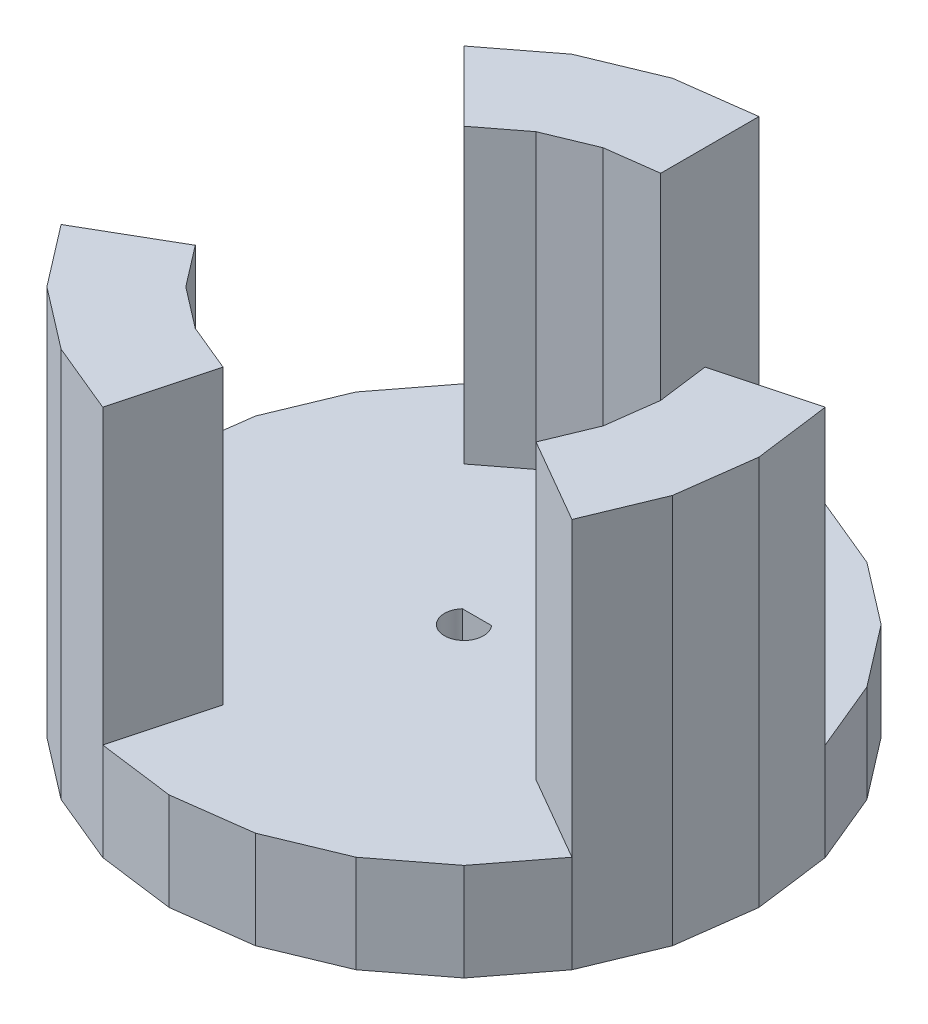
SolidWorks part; units mm, degrees
ref_plane "Front Plane" through (0, 0, 0) normal (0, 0, 1) x (1, 0, 0)
ref_plane "Top Plane" through (0, 0, 0) normal (0, 1, 0) x (1, 0, 0)
ref_plane "Right Plane" through (0, 0, 0) normal (1, 0, 0) x (0, 0, -1)
sketch "Sketch1" plane through (0, 0, 0) normal (0, 1, 0) x (1, 0, 0)
  line L0 (-14.2664, 14.2664) -> (-21.3898, 21.3898)
  line L1 (30.2497, 0) -> (29.219, 7.8292)
  line L2 (29.219, 7.8292) -> (26.197, 15.1248)
  line L3 (26.197, 15.1248) -> (21.3898, 21.3898)
  line L4 (21.3898, 21.3898) -> (15.1248, 26.197)
  line L5 (15.1248, 26.197) -> (7.8292, 29.219)
  line L6 (7.8292, 29.219) -> (0, 30.2497)
  line L7 (0, 30.2497) -> (-7.8292, 29.219)
  line L8 (-7.8292, 29.219) -> (-15.1248, 26.197)
  line L9 (-15.1248, 26.197) -> (-21.3898, 21.3898)
  line L10 (-21.3898, 21.3898) -> (-26.197, 15.1248)
  line L11 (-26.197, 15.1248) -> (-29.219, 7.8292)
  line L12 (-29.219, 7.8292) -> (-30.2497, 0)
  line L13 (-30.2497, 0) -> (-29.219, -7.8292)
  line L14 (-29.219, -7.8292) -> (-26.197, -15.1248)
  line L15 (-26.197, -15.1248) -> (-21.3898, -21.3898)
  line L16 (-21.3898, -21.3898) -> (-15.1248, -26.197)
  line L17 (-15.1248, -26.197) -> (-7.8292, -29.219)
  line L18 (-7.8292, -29.219) -> (0, -30.2497)
  line L19 (0, -30.2497) -> (7.8292, -29.219)
  line L20 (7.8292, -29.219) -> (15.1248, -26.197)
  line L21 (15.1248, -26.197) -> (21.3898, -21.3898)
  line L22 (21.3898, -21.3898) -> (26.197, -15.1248)
  line L23 (26.197, -15.1248) -> (29.219, -7.8292)
  line L24 (29.219, -7.8292) -> (30.2497, 0)
  line L25 (20.1758, 0) -> (19.4883, 5.2219)
  line L26 (19.4883, 5.2219) -> (17.4727, 10.0879)
  line L27 (17.4727, 10.0879) -> (14.2664, 14.2664)
  line L28 (14.2664, 14.2664) -> (10.0879, 17.4727)
  line L29 (10.0879, 17.4727) -> (5.2219, 19.4883)
  line L30 (5.2219, 19.4883) -> (0, 20.1758)
  line L31 (0, 20.1758) -> (-5.2219, 19.4883)
  line L32 (-5.2219, 19.4883) -> (-10.0879, 17.4727)
  line L33 (-10.0879, 17.4727) -> (-14.2664, 14.2664)
  line L34 (-14.2664, 14.2664) -> (-17.4727, 10.0879)
  line L35 (-17.4727, 10.0879) -> (-19.4883, 5.2219)
  line L36 (-19.4883, 5.2219) -> (-20.1758, 0)
  line L37 (-20.1758, 0) -> (-19.4883, -5.2219)
  line L38 (-19.4883, -5.2219) -> (-17.4727, -10.0879)
  line L39 (-17.4727, -10.0879) -> (-14.2664, -14.2664)
  line L40 (-14.2664, -14.2664) -> (-10.0879, -17.4727)
  line L41 (-10.0879, -17.4727) -> (-5.2219, -19.4883)
  line L42 (-5.2219, -19.4883) -> (0, -20.1758)
  line L43 (0, -20.1758) -> (5.2219, -19.4883)
  line L44 (5.2219, -19.4883) -> (10.0879, -17.4727)
  line L45 (10.0879, -17.4727) -> (14.2664, -14.2664)
  line L46 (14.2664, -14.2664) -> (17.4727, -10.0879)
  line L47 (17.4727, -10.0879) -> (19.4883, -5.2219)
  line L48 (19.4883, -5.2219) -> (20.1758, 0)
  line L49 (0, 20.1758) -> (0, 30.2497)
  line L50 (19.4883, 5.2219) -> (29.219, 7.8292)
  line L51 (17.4727, -10.0879) -> (26.197, -15.1248)
  line L52 (-5.2219, -19.4883) -> (-7.8292, -29.219)
  line L53 (-17.4727, -10.0879) -> (-26.197, -15.1248)
  line L54 (-1.4978, 1.3253) -> (1.4978, 1.3253)
  circle A0 centre (0, 0) radius 29.9909 construction
  circle A1 centre (0, 0) radius 20.0032 construction
  circle A2 centre (0, 0) radius 2
  point P55 (0, 0)
  point P56 (0, 0)
  point P57 (0, 0)
  point P58 (0, 0)
  point P59 (0, 0)
extrude "Boss-Extrude2" add sketch "Sketch1" along normal blind 10 contours L47 L48 L25 L26 L27 L28 L29 L30 L31 L32 L33 L34 L35 L36 L37 L38 L39 L40 L41 L42 L43 L44 L45 L46 A2 | L54 A2 region at (-11.8298, 0, -15.4169) region at (0, 0, -1.5995)
extrude "Boss-Extrude3" add sketch "Sketch1<5>" along normal blind 40 contours L39 L53 L15 L16 L17 L52 L41 L40 | L31 L49 L7 L8 L9 L0 L33 L32 | L47 L51 L23 L24 L1 L50 L25 L48 region at (-9.473, 0, -22.8699) region at (-15.0694, 0, 19.6388) region at (24.5424, 0, 3.2311)
sketch "Sketch1<5>" plane through (0, 0, 0) normal (0, 1, 0) x (1, 0, 0) same geometry as "Sketch1"
extrude "Boss-Extrude4" add sketch "Sketch1<7>" along normal blind 10 contours L53 L38 L37 L36 L35 L34 L0 L10 L11 L12 L13 L14 | L26 L50 L2 L3 L4 L5 L6 L49 L30 L29 L28 L27 | L42 L52 L18 L19 L20 L21 L22 L51 L46 L45 L44 L43 region at (-23.4248, 0, -3.0839) region at (14.3832, 0, -18.7445) region at (9.0416, 0, 21.8285)
sketch "Sketch1<7>" plane through (0, 0, 0) normal (0, 1, 0) x (1, 0, 0) same geometry as "Sketch1"
